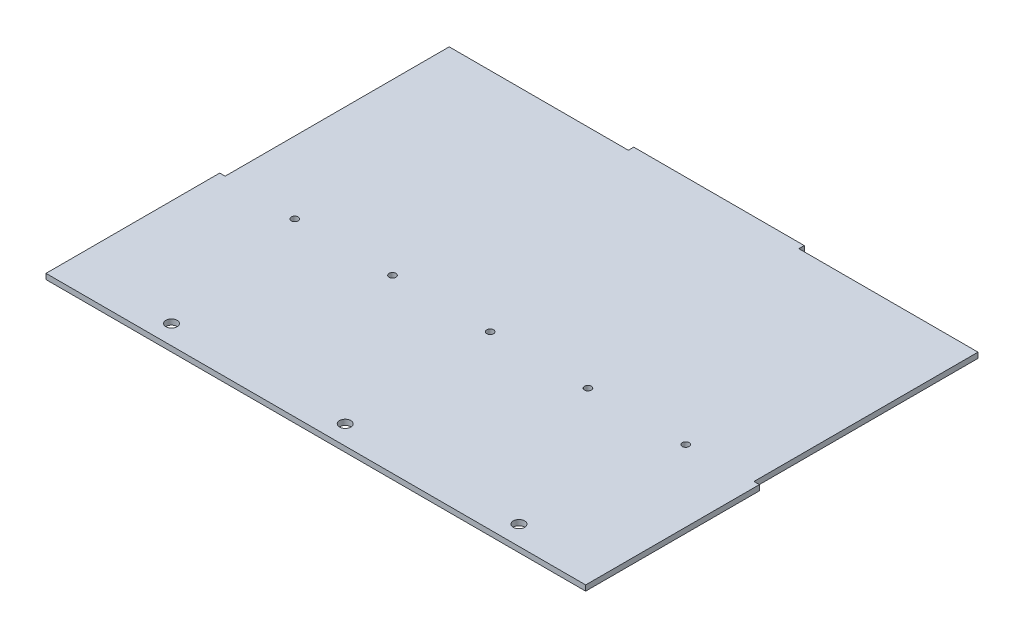
SolidWorks part; units mm, degrees
material "6061-T6 (SS)"
ref_plane "X-Y Datum" through (0, 0, 0) normal (0, 0, 1) x (1, 0, 0)
ref_plane "X-Z Datum" through (0, 0, 0) normal (0, 1, 0) x (1, 0, 0)
ref_plane "Y-Z Datum" through (0, 0, 0) normal (1, 0, 0) x (0, 0, -1)
sketch "Sketch1" plane through (0, 0, 0) normal (0, 0, 1) x (1, 0, 0)
  line L1 (-157.79, -1.5875) -> (157.79, -1.5875)
  line L2 (-157.79, -1.5875) -> (-157.79, 1.5875)
  line L3 (-157.79, 1.5875) -> (157.79, 1.5875)
  line L4 (157.79, -1.5875) -> (157.79, 1.5875)
  line L5 (-157.79, -1.5875) -> (157.79, 1.5875) construction
  line L6 (-157.79, 1.5875) -> (157.79, -1.5875) construction
  point P0 (0, 0)
  dimension "D1" = 315.58
  dimension "D2" = 3.175
extrude "Boss-Extrude1" add sketch "Sketch1" along normal blind 232.6
sketch "Sketch5" plane through (0, 1.5875, 0) normal (0, 1, 0) x (1, 0, 0)
  line L15 (-157.79, 0) -> (-154.615, 0)
  line L16 (-157.79, 0) -> (-157.79, -131)
  line L17 (-157.79, -131) -> (-154.615, -131)
  line L18 (-154.615, 0) -> (-154.615, -131)
  dimension "D3" = 3.175
  dimension "D4" = 131
extrude "Cut-Extrude2" cut sketch "Sketch5" against normal through all and the other way through all
mirror "Mirror1" about plane through (0, 0, 0) normal (1, 0, 0) of "Cut-Extrude2"
sketch "Sketch7" plane through (0, -1.5875, 0) normal (0, -1, 0) x (1, 0, 0)
  line L0 (110.4954, 221.3083) -> (104.4954, 221.3083) construction
  circle A0 centre (107.4954, 221.3083) radius 3.302
  dimension "D1" = 6.604
extrude "Cut-Extrude3" cut sketch "Sketch7" against normal through all
pattern_linear "LPattern1" count 3 spacing 101.6 along (-1, 0, 0) of "Cut-Extrude3"
sketch "Sketch8" plane through (0, -1.5875, 0) normal (0, -1, 0) x (1, 0, 0)
  line L0 (-154.615, 131) -> (-154.615, 0) construction
  line L2 (-157.79, 232.6) -> (157.79, 232.6) construction
  circle A0 centre (-112.6329, 132.2875) radius 2
  dimension "D1" = 41.9821
  dimension "D3" = 4
  dimension "D2" = 100.3125
extrude "Cut-Extrude4" cut sketch "Sketch8" against normal through all
pattern_linear "LPattern2" count 5 spacing 57.15 along (1, 0, 0) of "Cut-Extrude4"
sketch "Sketch10" plane through (0, 0, 0) normal (0, 0, -1) x (-1, 0, 0)
  line L0 (-154.615, -1.5875) -> (-154.615, 1.5875) construction
  line L2 (154.615, -1.5875) -> (154.615, 1.5875) construction
  line L4 (-154.615, 1.5875) -> (154.615, 1.5875) construction
  line L5 (-49.84, 1.5875) -> (49.84, 1.5875)
  line L6 (-49.84, 1.5875) -> (-49.84, -1.5875)
  line L7 (-49.84, -1.5875) -> (49.84, -1.5875)
  line L8 (49.84, 1.5875) -> (49.84, -1.5875)
  line L9 (154.615, -1.5875) -> (-154.615, -1.5875) construction
  dimension "D1" = 104.775
  dimension "D2" = 104.775
extrude "Boss-Extrude2" add sketch "Sketch10" along normal blind 3.175
